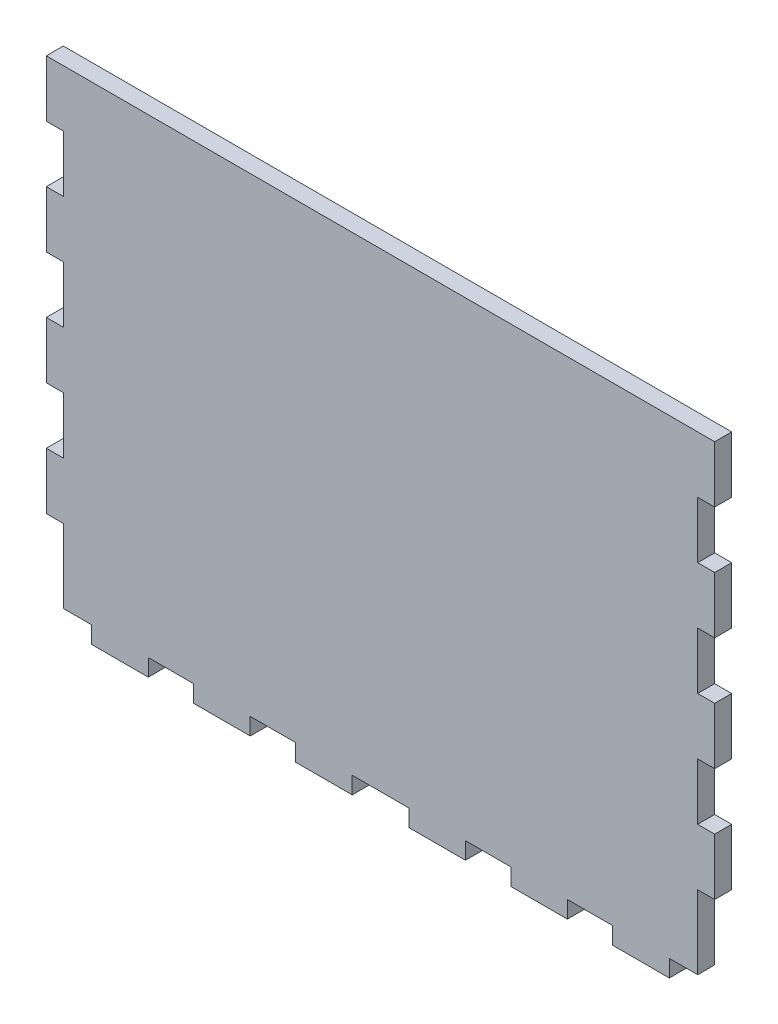
SolidWorks part; units mm, degrees
ref_plane "Front Plane" through (0, 0, 0) normal (0, 0, 1) x (1, 0, 0)
ref_plane "Top Plane" through (0, 0, 0) normal (0, 1, 0) x (1, 0, 0)
ref_plane "Right Plane" through (0, 0, 0) normal (1, 0, 0) x (0, 0, -1)
sketch "Sketch1" plane through (0, 0, 0) normal (0, 0, 1) x (1, 0, 0)
  line L0 (-56, 0) -> (56, 0) construction
  line L1 (0, -25.5) -> (0, 57.5) construction
  line L2 (-56, -12.5) -> (-56, -25.5)
  line L3 (-56, 57.5) -> (56, 57.5)
  line L4 (-59, -12.5) -> (-56, -12.5)
  line L5 (-23, -25.5) -> (-23, -28.5)
  line L6 (-59, -2.5) -> (-59, -12.5)
  line L7 (-56, -2.5) -> (-59, -2.5)
  line L8 (-56, 57.5) -> (-59, 57.5)
  line L9 (-59, 57.5) -> (-59, 47.5)
  line L10 (-59, 47.5) -> (-56, 47.5)
  line L11 (-56, 47.5) -> (-56, 37.5)
  line L12 (-56, 37.5) -> (-59, 37.5)
  line L13 (-59, 37.5) -> (-59, 27.5)
  line L14 (59, 17.5) -> (59, 7.5)
  line L15 (-59, 27.5) -> (-56, 27.5)
  line L16 (-56, 27.5) -> (-56, 17.5)
  line L17 (56, 7.5) -> (59, 7.5)
  line L18 (56, 17.5) -> (59, 17.5)
  line L19 (56, 7.5) -> (56, -2.5)
  line L20 (56, 27.5) -> (56, 17.5)
  line L21 (59, 27.5) -> (56, 27.5)
  line L22 (59, 37.5) -> (59, 27.5)
  line L23 (56, 37.5) -> (59, 37.5)
  line L24 (56, 47.5) -> (56, 37.5)
  line L25 (59, 47.5) -> (56, 47.5)
  line L26 (59, 57.5) -> (59, 47.5)
  line L27 (56, 57.5) -> (59, 57.5)
  line L28 (-5, -25.5) -> (5, -25.5)
  line L29 (-23, -28.5) -> (-33, -28.5)
  line L30 (-5, -25.5) -> (-5, -28.5)
  line L31 (-5, -28.5) -> (-15, -28.5)
  line L32 (-15, -25.5) -> (-15, -28.5)
  line L33 (-33, -25.5) -> (-33, -28.5)
  line L34 (-41, -25.5) -> (-41, -28.5)
  line L35 (-41, -28.5) -> (-51, -28.5)
  line L36 (-51, -25.5) -> (-51, -28.5)
  line L37 (-23, -25.5) -> (-15, -25.5)
  line L38 (-33, -25.5) -> (-41, -25.5)
  line L39 (-51, -25.5) -> (-56, -25.5)
  line L40 (51, -25.5) -> (56, -25.5)
  line L41 (33, -25.5) -> (41, -25.5)
  line L42 (23, -25.5) -> (15, -25.5)
  line L43 (51, -25.5) -> (51, -28.5)
  line L44 (41, -28.5) -> (51, -28.5)
  line L45 (41, -25.5) -> (41, -28.5)
  line L46 (33, -25.5) -> (33, -28.5)
  line L47 (15, -25.5) -> (15, -28.5)
  line L48 (5, -28.5) -> (15, -28.5)
  line L49 (5, -25.5) -> (5, -28.5)
  line L50 (23, -28.5) -> (33, -28.5)
  line L51 (23, -25.5) -> (23, -28.5)
  line L52 (56, -2.5) -> (59, -2.5)
  line L53 (59, -2.5) -> (59, -12.5)
  line L54 (59, -12.5) -> (56, -12.5)
  line L55 (56, -12.5) -> (56, -25.5)
  line L56 (-56, 7.5) -> (-56, -2.5)
  line L57 (-56, 17.5) -> (-59, 17.5)
  line L58 (-56, 7.5) -> (-59, 7.5)
  line L59 (-59, 17.5) -> (-59, 7.5)
  point P58 (-48.9103, 40.41)
  dimension "D2" = 25.5
  dimension "D3" = 5
  dimension "D4" = 83
  dimension "D5" = 10
  dimension "D6" = 112
  dimension "D8" = 10
  dimension "D9" = 3
  dimension "D10" = 3
  dimension "D11" = 10
  dimension "D7" = 10
  dimension "D13" = 10
  dimension "D12" = 10
  dimension "D16" = 10
  dimension "D17" = 10
  dimension "D18" = 3
extrude "Boss-Extrude1" add sketch "Sketch1" along normal blind 3
